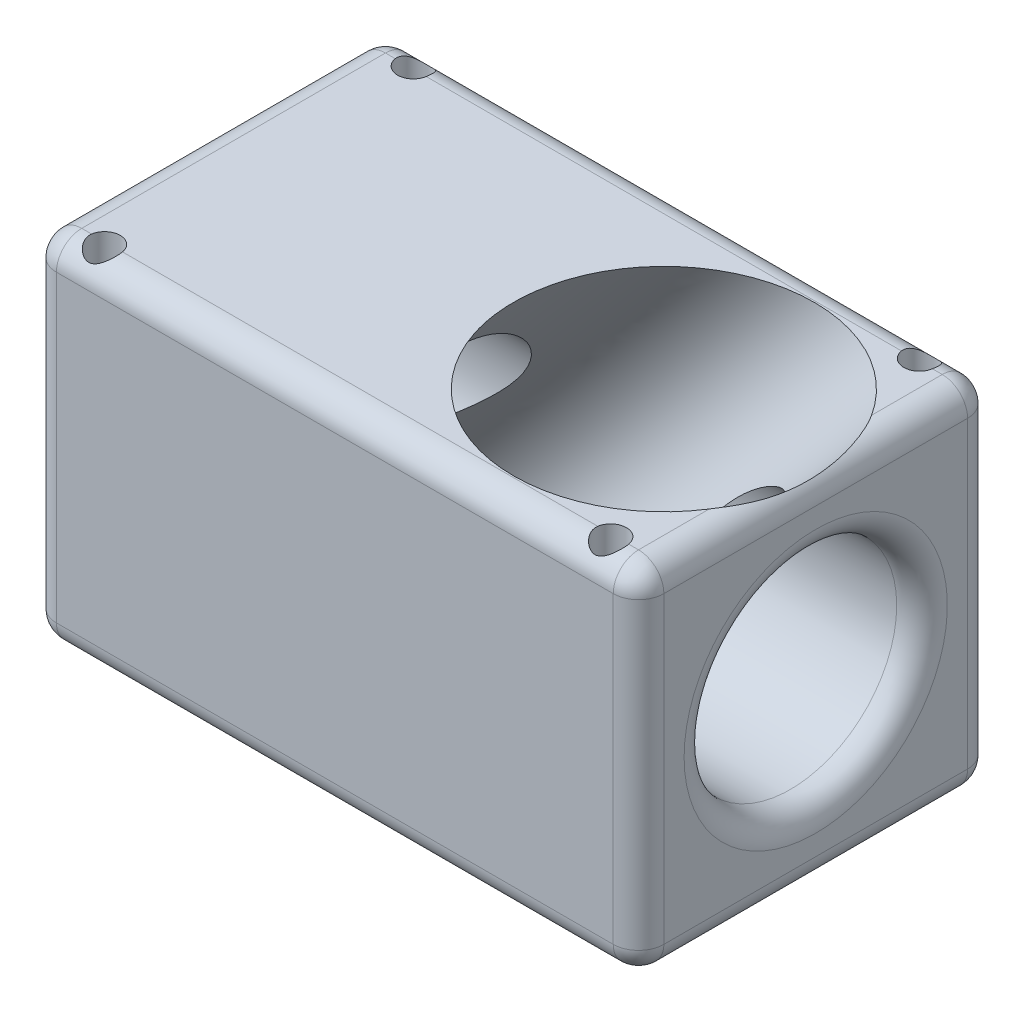
SolidWorks part; units mm, degrees
ref_plane "Front Plane" through (0, 0, 0) normal (0, 0, 1) x (1, 0, 0)
ref_plane "Top Plane" through (0, 0, 0) normal (0, 1, 0) x (1, 0, 0)
ref_plane "Right Plane" through (0, 0, 0) normal (1, 0, 0) x (0, 0, -1)
sketch "Sketch1" plane through (0, 0, 0) normal (0, 1, 0) x (1, 0, 0)
  line L1 (-30, -17.5) -> (30, -17.5)
  line L2 (-30, -17.5) -> (-30, 17.5)
  line L3 (-30, 17.5) -> (30, 17.5)
  line L4 (30, -17.5) -> (30, 17.5)
  line L5 (-30, -17.5) -> (30, 17.5) construction
  line L6 (-30, 17.5) -> (30, -17.5) construction
  point P0 (0, 0)
  dimension "D1" = 60
  dimension "D2" = 35
extrude "Boss-Extrude1" add sketch "Sketch1" along normal blind 35
sketch "Sketch2" plane through (-30, 0, 0) normal (-1, 0, 0) x (0, 0, 1)
  circle A0 centre (0, 17.5) radius 10.5
  dimension "D1" = 21
extrude "Cut-Extrude1" cut sketch "Sketch2" against normal up to surface (60 mm away) up to face at (30, 17.5, 0)
sketch "Sketch3" plane through (0, 35, 0) normal (0, 1, 0) x (1, 0, 0)
  circle A0 centre (-25, 15.25) radius 1.55
  circle A1 centre (25, 15.25) radius 1.55
  circle A3 centre (-25, -15.25) radius 1.55
  circle A4 centre (25, -15.25) radius 1.55
  dimension "D1" = 50
  dimension "D2" = 30.5
  dimension "D3" = 3.1
  dimension "D4" = 3.1
  dimension "D5" = 3.1
  dimension "D6" = 3.1
  dimension "D7" = 15.25
  dimension "D8" = 25
extrude "Cut-Extrude2" cut sketch "Sketch3" against normal up to surface (35 mm away) up to face at (0, 0, 0)
fillet "Fillet1" radius 2.5 14 edges at (30, 35, 0) (0, 35, 17.5) (30, 17.5, 17.5) (0, 0, 17.5) (30, 0, 0) (30, 17.5, -17.5) (0, 35, -17.5) (0, 0, -17.5) (-30, 17.5, -17.5) (-30, 35, 0) (-30, 17.5, 17.5) (-30, 0, 0) (-30, 17.5, 10.5) (30, 17.5, 10.5)
sketch "Sketch4" plane through (0, 35, 0) normal (0, 1, 0) x (1, 0, 0)
  circle A1 centre (15, 0) radius 14.8492
  dimension "D1" = 29.6985
  dimension "D2" = 15
sketch "Sketch6" plane through (0, 0, 0) normal (0, 1, 0) x (1, 0, 0)
  circle A0 centre (-15, 0) radius 14.8492
  dimension "D1" = 29.6985
  dimension "D2" = 15
loft "Cut-Loft1" cut profiles "Sketch6", "Sketch4" connector at (-0.1511, 0, -0.1072) connector at (29.8409, 35, -0.4977)
